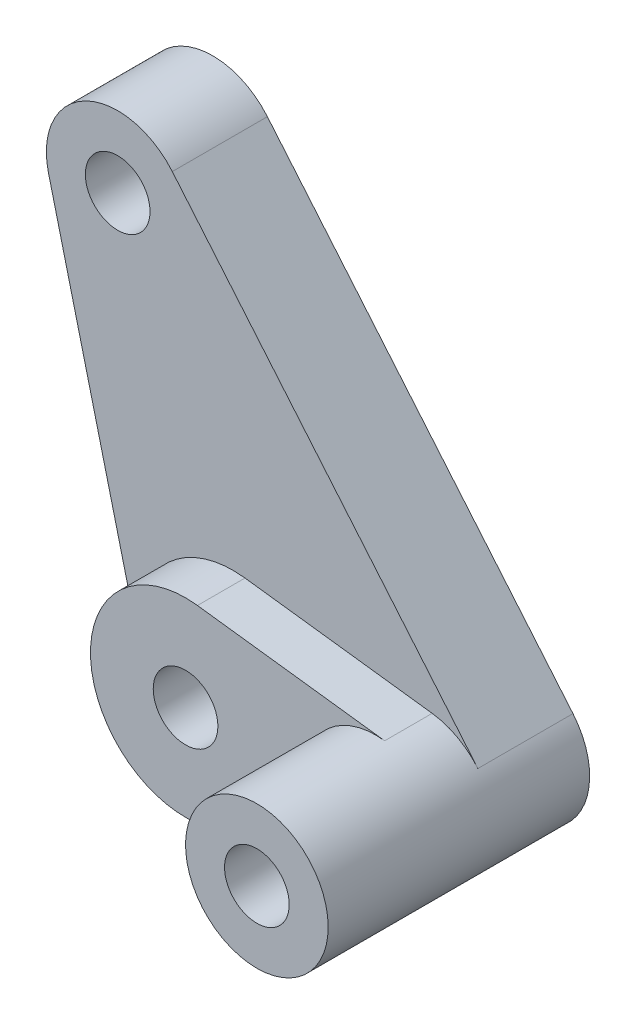
SolidWorks part; units mm, degrees
ref_plane "Front Plane" through (0, 0, 0) normal (0, 0, 1) x (1, 0, 0)
ref_plane "Top Plane" through (0, 0, 0) normal (0, 1, 0) x (1, 0, 0)
ref_plane "Right Plane" through (0, 0, 0) normal (1, 0, 0) x (0, 0, -1)
sketch "Sketch1" plane through (0, 0, 0) normal (0, 0, 1) x (1, 0, 0)
  line L0 (-12.7, 0) -> (0, 0) construction
  line L1 (0.5953, -4.7251) -> (-11.9062, -6.3002)
  line L3 (-20.4085, 24.3219) -> (0, 0) construction
  line L5 (3.6483, 3.0613) -> (-16.7602, 27.3832)
  line L6 (-25.0292, 23.1683) -> (-18.8609, -1.5381)
  line L7 (0, 0) -> (-20.4085, 24.3219) construction
  arc A0 (0.5953, -4.7251) -> (3.6483, 3.0613) centre (0, 0) ccw
  arc A1 (-18.8609, -1.5381) -> (-11.9062, -6.3002) centre (-12.7, 0) ccw
  arc A3 (-16.7602, 27.3832) -> (-25.0292, 23.1683) centre (-20.4085, 24.3219) ccw
  circle A4 centre (-12.7, 0) radius 2.159
  circle A5 centre (-20.4085, 24.3219) radius 2.159
  circle A6 centre (0, 0) radius 2.159
  dimension "D3" = 4.318
  dimension "D4" = 4.7625
  dimension "D5" = 6.35
  dimension "D6" = 4.7625
  dimension "D1" = 12.7
  dimension "D2" = 31.75
  dimension "D7" = 50
extrude "Boss-Extrude1" add sketch "Sketch1" along normal mid plane 6.35
sketch "Sketch3" plane through (0, 0, 3.175) normal (0, 0, 1) x (1, 0, 0)
  circle A0 centre (0, 0) radius 4.7625
  circle A1 centre (0, 0) radius 2.159 construction
  circle A2 centre (0, 0) radius 2.159
extrude "Boss-Extrude2" add sketch "Sketch3" along normal blind 11.1125
sketch "Sketch4" plane through (0, 0, -3.175) normal (0, 0, -1) x (-1, 0, 0)
  line L1 (12.7, 5.1326) -> (8.255, 2.5663)
  line L2 (8.255, 2.5663) -> (8.255, -2.5663)
  line L3 (8.255, -2.5663) -> (12.7, -5.1326)
  line L4 (12.7, -5.1326) -> (17.145, -2.5663)
  line L5 (17.145, -2.5663) -> (17.145, 2.5663)
  line L6 (17.145, 2.5663) -> (12.7, 5.1326)
  circle A0 centre (12.7, 0) radius 4.445 construction
  dimension "D1" = 8.89
extrude "Cut-Extrude1" cut sketch "Sketch4" against normal blind 3.175
sketch "Sketch5" plane through (0, 0, 3.175) normal (0, 0, 1) x (1, 0, 0)
  line L0 (-11.9062, 6.3002) -> (0.5953, 4.7251)
  line L1 (-11.9062, -6.3002) -> (0.5953, -4.7251) construction
  line L2 (-11.9062, -6.3002) -> (0.5953, -4.7251)
  arc A0 (-11.9062, 6.3002) -> (-11.9062, -6.3002) centre (-12.7, 0) ccw
  circle A1 centre (0, 0) radius 4.7625 construction
  arc A2 (0.5953, 4.7251) -> (0.5953, -4.7251) centre (0, 0) ccw
  arc A3 (-18.8609, -1.5381) -> (-11.9062, -6.3002) centre (-12.7, 0) ccw construction
  circle A4 centre (-12.7, 0) radius 2.159 construction
  circle A5 centre (-12.7, 0) radius 2.159
extrude "Boss-Extrude3" add sketch "Sketch5" along normal blind 3.175
